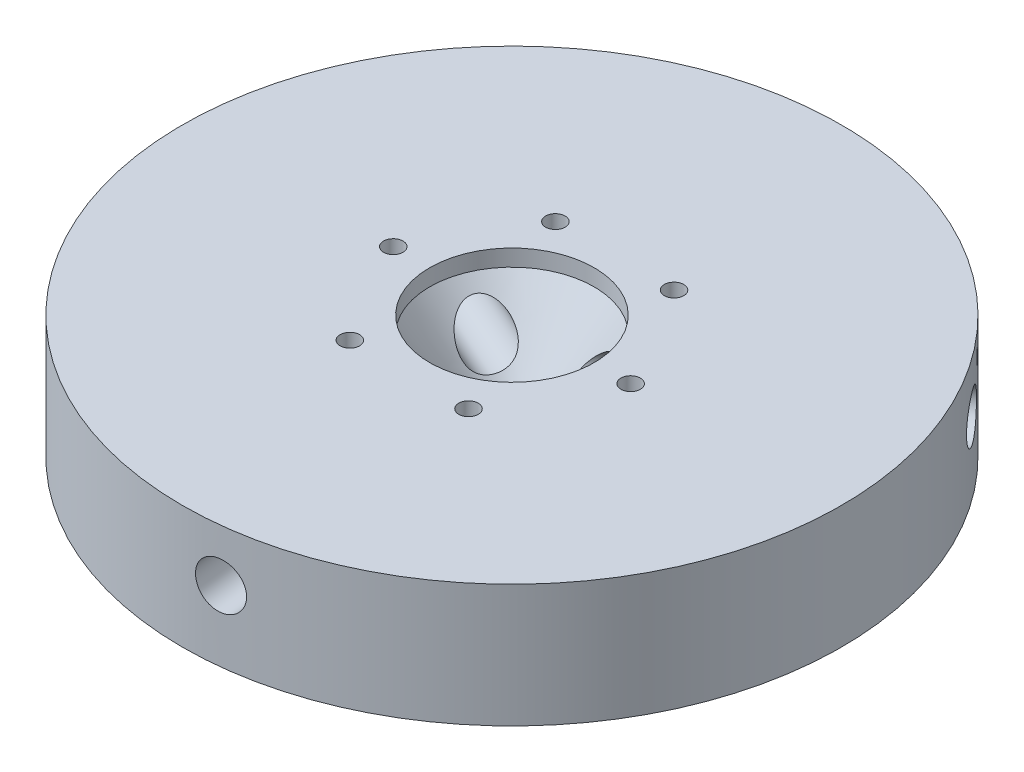
SolidWorks part; units mm, degrees
other "DetailItem2"
ref_plane "Front Plane" through (0, 0, 0) normal (0, 0, 1) x (1, 0, 0)
ref_plane "Top Plane" through (0, 0, 0) normal (0, 1, 0) x (1, 0, 0)
ref_plane "Right Plane" through (0, 0, 0) normal (1, 0, 0) x (0, 0, -1)
sketch "Sketch1" plane through (0, 0, 0) normal (0, 1, 0) x (1, 0, 0)
  circle A0 centre (0, 0) radius 80.54
  dimension "D1" = 161.08
extrude "Boss-Extrude1" add sketch "Sketch1" along normal blind 30
sketch "Sketch2" plane through (0, 0, 0) normal (0, 0, 1) x (1, 0, 0)
  line L0 (-4.3078, 0) -> (-4.3078, 5.327)
  line L2 (-20.1026, 25.9476) -> (-20.1026, 30)
  line L3 (80.54, 30) -> (-80.54, 30) construction
  line L4 (-20.1026, 30) -> (0, 30)
  line L5 (0, 30) -> (0, 0)
  line L6 (0, 0) -> (-4.3078, 0)
  line L8 (-4.3078, 5.327) -> (-20.1026, 25.9476)
  point P15 (-4.9029, 7)
  dimension "Fuel Outlet Radius" = 4.3078
  dimension "Fuel Chamber Radius" = 20.1026
revolve "Cut-Revolve1" cut sketch "Sketch2" angle 360 about L5
sketch "Sketch12" plane through (0, 30, 0) normal (0, 1, 0) x (1, 0, 0)
  line L0 (0, 0) -> (0, 60.61)
  line L1 (0, 0) -> (30.305, 52.4898)
  circle A0 centre (0, 0) radius 60.61
  dimension "D1" = 121.22
  dimension "D2" = 30
sketch "Sketch30" plane through (0, 0, 0) normal (0, -1, 0) x (1, 0, 0)
sketch "Sketch21" plane through (0, 0, 0) normal (0, 0, 1) x (1, 0, 0)
  line L0 (-80.54, 0) -> (80.54, 0) construction
  line L1 (60, 0) -> (65, 0)
  line L2 (60, 0) -> (60, 3)
  line L3 (60, 3) -> (65, 3)
  line L4 (65, 0) -> (65, 3)
  line L5 (0, 0) -> (0, -8.9782) construction
  dimension "D1" = 60
  dimension "D2" = 5
  dimension "D3" = 3
revolve "Cut-Revolve2" cut sketch "Sketch21" angle 360 about L5
hole_wizard "3/16 (0.1875) Diameter Hole1" positions "Sketch27" profile "Sketch28" hole size "3/16" standard "ANSI Inch"
sketch "Sketch27" plane through (0, 30, 0) normal (0, 1, 0) x (1, 0, 0)
  point P0 (29, 0)
  dimension "D1" = 29
sketch "Sketch28" plane through (29, 30, 0) normal (1, 0, 0) x (0, 0, 1)
  line L0 (0, 0) -> (0, 13.4308)
  line L1 (0, 13.4308) -> (2.3812, 12)
  line L2 (2.3812, 12) -> (2.3812, 0)
  line L5 (2.3812, 0) -> (0, 0)
  line L10 (0, 13.4308) -> (-2.3813, 12) construction
  line L11 (0, -6.35) -> (0, 107.95) construction
  dimension "Hole Dia." = 4.7625
  dimension "Hole Depth" = 12
  dimension "Drill Angle" = 118
pattern_circular "CirPattern4" count 6 over 360 about axis through (0, 30, 0) along (0, -1, 0) of "3/16 (0.1875) Diameter Hole1" reverse direction yes
sketch "Sketch34" plane through (0, 30, 0) normal (0, 1, 0) x (1, 0, 0)
  line L0 (0, 0) -> (8.8002, -80.0578) construction
  circle A0 centre (0, 0) radius 80.54 construction
ref_plane "Plane3" through (8.8002, 30, 80.0578) normal (0.1093, 0, 0.994) x (0.994, 0, -0.1093)
sketch "Sketch35" plane through (8.8002, 30, 80.0578) normal (0.1093, 0, 0.994) x (0.994, 0, -0.1093)
  line L0 (0, -0.0242) -> (0, -30) construction
  point P3 (0, -15.0121)
sketch "Sketch37" plane through (8.8002, 30, 80.0578) normal (0.1093, 0, 0.994) x (0.994, 0, -0.1093)
  circle A1 centre (0, -12.8016) radius 5.6602
extrude "Cut-Extrude1" cut sketch "Sketch37" against normal blind 80
pattern_circular "CirPattern6" count 3 over 360 about axis through (0, 30, 0) along (0, 1, 0) of "Cut-Extrude1"
pattern_circular "CirPattern7" count 3 over 360 rebuild error yes
